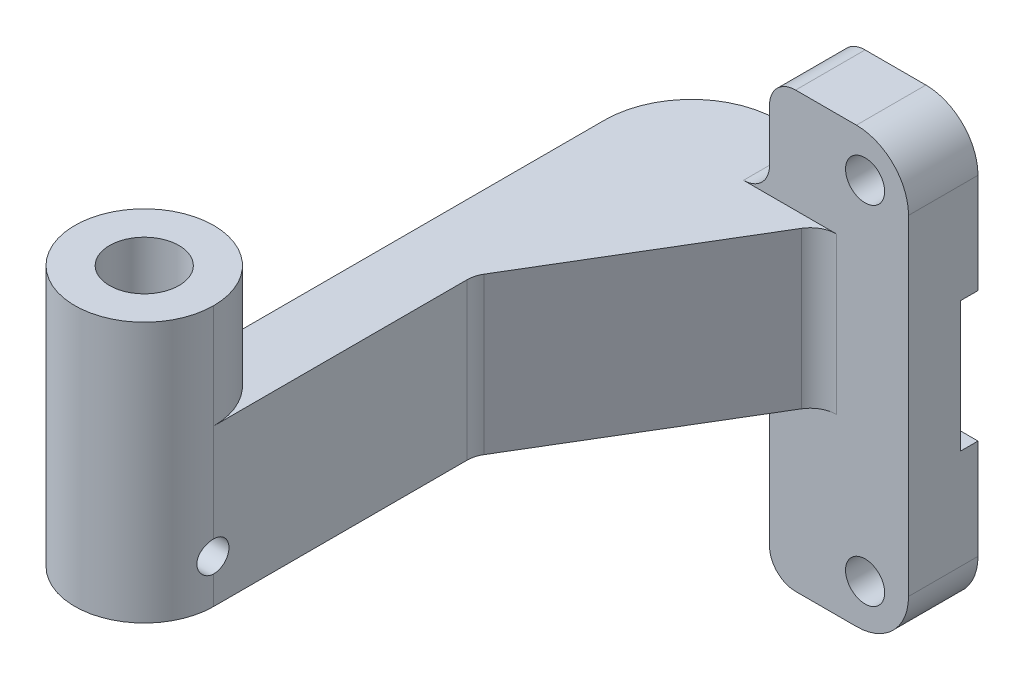
SolidWorks part; units mm, degrees
ref_plane "前视基准面" through (0, 0, 0) normal (0, 0, 1) x (1, 0, 0)
ref_plane "上视基准面" through (0, 0, 0) normal (0, 1, 0) x (1, 0, 0)
ref_plane "右视基准面" through (0, 0, 0) normal (1, 0, 0) x (0, 0, -1)
sketch "草图1" plane through (0, 0, 0) normal (0, 0, 1) x (1, 0, 0)
  line L1 (-30, 25) -> (30, 25)
  line L2 (-30, 25) -> (-30, -25)
  line L3 (-30, -25) -> (30, -25)
  line L4 (30, 25) -> (30, -25)
  line L5 (0, -25) -> (0, 25) construction
  line L6 (-30, 0) -> (30, 0) construction
  point P0 (0, 0)
  dimension "D1" = 50
  dimension "D2" = 60
extrude "凸台-拉伸1" [suppressed] add sketch "草图1" along normal blind 10
sketch "草图2" [suppressed] plane through (0, 0, 10) normal (0, 0, 1) x (1, 0, 0)
  line L0 (-7.0821, 0) -> (36.7179, 0) construction
  line L1 (0, 12.9112) -> (0, -14.5455) construction
  line L2 (-30, 25) -> (-30, -25) construction
  circle A0 centre (20, 20) radius 2
  circle A1 centre (20, -20) radius 2
  dimension "D1" = 4
  dimension "D2" = 40
  dimension "D3" = 50
extrude "切除-拉伸1" [suppressed] cut sketch "草图2" against normal blind 10
sketch "草图3" [suppressed] plane through (0, 25, 0) normal (0, 1, 0) x (1, 0, 0)
  circle A0 centre (-30, -10) radius 10
  dimension "D1" = 20
extrude "凸台-拉伸2" [suppressed] add sketch "草图3" against normal blind 50
sketch "草图4" [suppressed] plane through (0, 25, 0) normal (0, 1, 0) x (1, 0, 0)
  circle A0 centre (-30, -10) radius 4.25
  dimension "D1" = 8.5
extrude "切除-拉伸2" [suppressed] cut sketch "草图4" against normal blind 50
sketch "草图5" [suppressed] plane through (0, 0, 0) normal (0, 0, -1) x (-1, 0, 0)
  line L0 (30, 25) -> (30, -25) construction
  circle A0 centre (30, 0) radius 1.5
  dimension "D1" = 3
extrude "切除-拉伸3" [suppressed] cut sketch "草图5" against normal blind 50
sketch "草图6" plane through (0, 0, 0) normal (0, 1, 0) x (1, 0, 0)
  line L0 (0, 0) -> (-25, 0)
  line L1 (-25, 0) -> (-25, -55)
  line L2 (-33, -47) -> (-33, 8)
  line L3 (-33, 8) -> (0, 8)
  line L4 (0, 8) -> (0, 0)
  arc A0 (-25, -55) -> (-41, -55) centre (-33, -55) cw
  arc A1 (-41, -55) -> (-33, -47) centre (-33, -55) cw
  circle A2 centre (-33, -55) radius 4
  dimension "D1" = 8
  dimension "D3" = 55
  dimension "D5" = 8
  dimension "D2" = 8
  dimension "D4" = 25
extrude "凸台-拉伸3" add sketch "草图6" along normal mid plane 50
fillet "圆角1" radius 10 1 edges at (-33, 0, -8)
fillet "圆角2" radius 3 1 edges at (-25, 0, 0)
sketch "草图7" plane through (0, 0, -8) normal (0, 0, -1) x (-1, 0, 0)
  line L0 (5, 25) -> (5, -25) construction
  line L3 (0, 0) -> (15.9365, 0) construction
  line L4 (0, 25) -> (0, -25) construction
  circle A0 centre (5, 20) radius 2.25
  circle A1 centre (5, -20) radius 2.25
  dimension "D1" = 4.5
  dimension "D2" = 40
  dimension "D3" = 5
extrude "切除-拉伸4" cut sketch "草图7" against normal blind 50
sketch "草图8" plane through (-25, 0, 0) normal (1, 0, 0) x (0, 0, -1)
  line L0 (-55, 25) -> (-55, -25) construction
  circle A0 centre (-55, 0) radius 1.75
  dimension "D1" = 3.5
extrude "切除-拉伸5" cut sketch "草图8" against normal blind 50
sketch "草图9" plane through (0, 0, 0) normal (0, 1, 0) x (1, 0, 0)
  line L0 (-10, 0) -> (-25, -25)
  line L1 (-25, -55) -> (-25, -3) construction
  line L2 (-22, 0) -> (0, 0) construction
  line L3 (-22, 0) -> (-10, 0)
  line L4 (-25, -25) -> (-25, -3)
  arc A4 (-22, 0) -> (-25, -3) centre (-22, -3) ccw construction
  arc A5 (-22, 0) -> (-25, -3) centre (-22, -3) ccw
  circle A6 centre (-33, -55) radius 4 construction
  dimension "D1" = 30
  dimension "D2" = 10
extrude "凸台-拉伸4" add sketch "草图9" along normal mid plane 10
fillet "圆角5" radius 3 2 edges at (-25, 0, 25) (-10, 0, 0)
fillet "圆角6" radius 6 2 edges at (0, 25, -4) (0, -25, -4)
sketch "草图11" plane through (-33, 0, 0) normal (-1, 0, 0) x (0, 0, 1)
  line L0 (-8, -25) -> (-8, 25) construction
  line L1 (47, 25) -> (-8, 25)
  line L2 (47, 25) -> (47, 13)
  line L3 (47, 13) -> (-8, 13)
  line L4 (-8, 25) -> (-8, 13)
  line L5 (-15.0098, 0) -> (67.1359, 0) construction
  line L6 (-8, -25) -> (-8, -13)
  line L7 (47, -13) -> (-8, -13)
  line L8 (47, -25) -> (47, -13)
  line L9 (47, -25) -> (-8, -25)
  dimension "D1" = 12
extrude "切除-拉伸7" cut sketch "草图11" against normal blind 17
sketch "草图12" plane through (0, 0, 0) normal (0, 0, 1) x (1, 0, 0)
  line L0 (-16, -13) -> (-16, -25) construction
  line L1 (-46.2778, -5) -> (-16, -5)
  line L2 (-46.2778, -5) -> (-46.2778, -26.6426)
  line L3 (-46.2778, -26.6426) -> (-16, -26.6426)
  line L4 (-16, -5) -> (-16, -26.6426)
  line L5 (-8.3014, -5) -> (-22, -5) construction
extrude "切除-拉伸8" cut sketch "草图12" against normal through all both and the other way through all
fillet "圆角7" radius 8 1 edges at (-25, 19, 47)
fillet "圆角8" radius 3 2 edges at (-16, 13, -4) (-16, 25, -4)
fillet "圆角9" radius 1 1 edges at (-33, 4, 47)
fillet "圆角10" radius 3 2 edges at (-16, -5, -4) (-16, -25, -4)
sketch "草图13" plane through (0, 5, 0) normal (0, 1, 0) x (1, 0, 0)
  line L3 (-8.3014, 0) -> (-22, 0)
  line L4 (-25, -3) -> (-25, -25.831)
  line L5 (-24.5725, -24.2875) -> (-10.8739, -1.4565)
  line L6 (-8.3014, 0) -> (-22, 0)
  line L7 (-25, -3) -> (-25, -25.831)
  line L8 (-24.5725, -24.2875) -> (-10.8739, -1.4565)
  arc A3 (-22, 0) -> (-25, -3) centre (-22, -3) ccw
  arc A4 (-24.5725, -24.2875) -> (-25, -25.831) centre (-22, -25.831) ccw
  arc A5 (-8.3014, 0) -> (-10.8739, -1.4565) centre (-8.3014, -3) ccw
  arc A6 (-22, 0) -> (-25, -3) centre (-22, -3) ccw
  arc A7 (-24.5725, -24.2875) -> (-25, -25.831) centre (-22, -25.831) ccw
  arc A8 (-8.3014, 0) -> (-10.8739, -1.4565) centre (-8.3014, -3) ccw
  dimension "D1" = 0
extrude "凸台-拉伸5" add sketch "草图13" along normal up to surface (8 mm away) up to face at (-26.6735, 13, 17.9913)
sketch "草图14" plane through (0, 0, -8) normal (0, 0, -1) x (-1, 0, 0)
  line L1 (-15, -7.5) -> (15, -7.5)
  line L2 (-15, -7.5) -> (-15, 7.5)
  line L3 (-15, 7.5) -> (15, 7.5)
  line L4 (15, -7.5) -> (15, 7.5)
  line L5 (0, 7.5) -> (0, -7.5) construction
  line L6 (-15, 0) -> (15, 0) construction
  point P0 (0, 0)
  dimension "D1" = 15
  dimension "D2" = 30
extrude "切除-拉伸9" cut sketch "草图14" against normal blind 2
